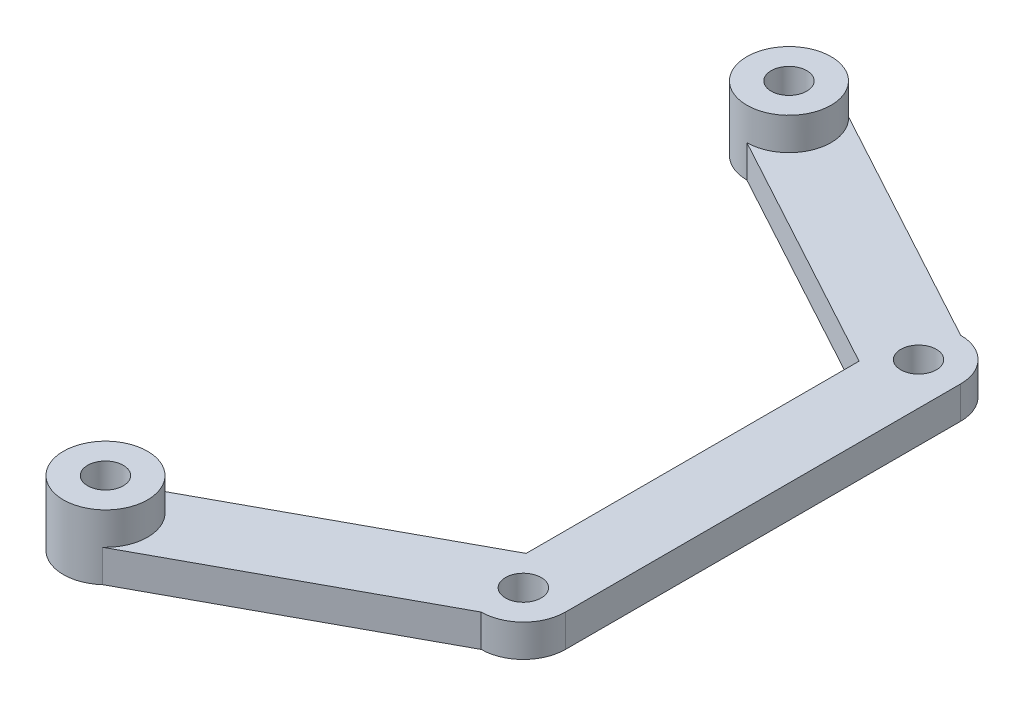
SolidWorks part; units mm, degrees
ref_plane "Front Plane" through (0, 0, 0) normal (0, 0, 1) x (1, 0, 0)
ref_plane "Top Plane" through (0, 0, 0) normal (0, 1, 0) x (1, 0, 0)
ref_plane "Right Plane" through (0, 0, 0) normal (1, 0, 0) x (0, 0, -1)
sketch "Sketch1" plane through (0, 0, 0) normal (0, 1, 0) x (1, 0, 0)
  line L1 (36.375, -26.375) -> (-36.375, -26.375) construction
  line L2 (36.375, -26.375) -> (36.375, 26.375) construction
  line L3 (36.375, 26.375) -> (-36.375, 26.375) construction
  line L4 (-36.375, -26.375) -> (-36.375, 26.375) construction
  line L5 (36.375, -26.375) -> (-36.375, 26.375) construction
  line L6 (36.375, 26.375) -> (-36.375, -26.375) construction
  circle A0 centre (-36.375, 26.375) radius 1.25
  point P0 (0, 0)
  dimension "D3" = 2.5
  dimension "D1" = 72.75
  dimension "D2" = 52.75
sketch "Sketch2" plane through (0, 0, 0) normal (0, 1, 0) x (1, 0, 0)
  line L1 (15.25, -15.25) -> (-15.25, -15.25) construction
  line L2 (15.25, -15.25) -> (15.25, 15.25) construction
  line L3 (15.25, 15.25) -> (-15.25, 15.25) construction
  line L4 (-15.25, -15.25) -> (-15.25, 15.25) construction
  line L5 (15.25, -15.25) -> (-15.25, 15.25) construction
  line L6 (15.25, 15.25) -> (-15.25, -15.25) construction
  circle A0 centre (-15.25, 15.25) radius 1.375
  point P0 (0, 0)
  dimension "D2" = 2.75
  dimension "D1" = 30.5
sketch "Sketch3" plane through (0, 0, 0) normal (0, 1, 0) x (1, 0, 0)
  line L0 (-36.375, 23.125) -> (-17.4387, 12.8475)
  line L1 (-34.1863, 28.7775) -> (-15.25, 18.5)
  line L2 (-36.375, -23.125) -> (-17.4387, -12.8475)
  line L3 (-34.1863, -28.7775) -> (-15.25, -18.5)
  line L4 (-17.4387, 12.8475) -> (-17.4387, -12.8475)
  line L5 (-12, 15.25) -> (-12, -15.25)
  arc A0 (-34.1863, 28.7775) -> (-36.375, 23.125) centre (-36.375, 26.375) ccw
  arc A1 (-12, 15.25) -> (-15.25, 18.5) centre (-15.25, 15.25) ccw
  arc A3 (-36.375, -23.125) -> (-34.1863, -28.7775) centre (-36.375, -26.375) ccw
  arc A4 (-15.25, -18.5) -> (-12, -15.25) centre (-15.25, -15.25) ccw
  circle A5 centre (-36.375, 26.375) radius 1.375
  circle A6 centre (-15.25, 15.25) radius 1.375
  circle A7 centre (-15.25, -15.25) radius 1.375
  circle A8 centre (-36.375, -26.375) radius 1.375
  dimension "D1" = 6.5
  dimension "D2" = 21.5455
  dimension "D4" = 2.75
extrude "Boss-Extrude1" add sketch "Sketch3" along normal blind 2.5
sketch "Sketch4" plane through (0, 2.5, 0) normal (0, 1, 0) x (1, 0, 0)
  circle A0 centre (-36.375, 26.375) radius 3.25
  circle A1 centre (-36.375, 26.375) radius 1.375
  circle A2 centre (-36.375, -26.375) radius 3.25
  circle A3 centre (-36.375, -26.375) radius 1.375
  dimension "D1" = 6.5
  dimension "D2" = 2.75
extrude "Boss-Extrude2" add sketch "Sketch4" along normal blind 2.5
